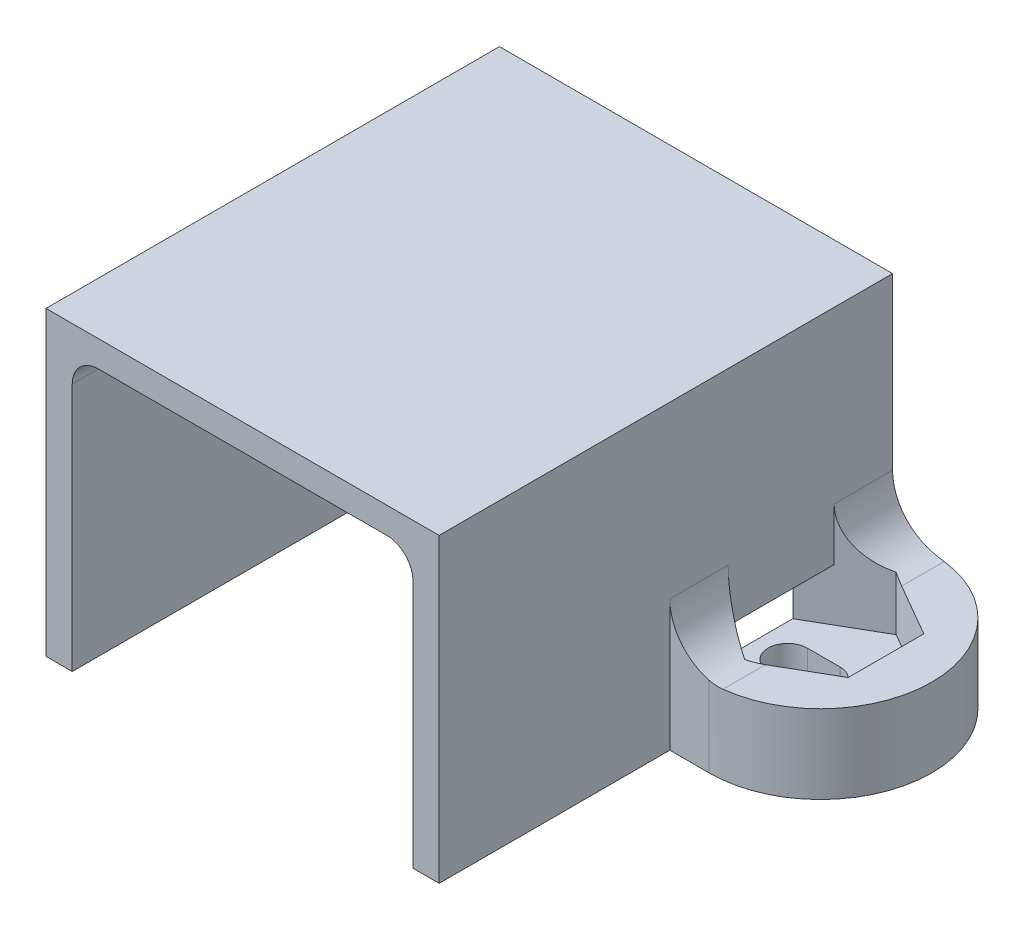
SolidWorks part; units mm, degrees
material "ABS"
ref_plane "Front" through (0, 0, 0) normal (0, 0, 1) x (1, 0, 0)
ref_plane "Top" through (0, 0, 0) normal (0, 1, 0) x (1, 0, 0)
ref_plane "Right" through (0, 0, 0) normal (1, 0, 0) x (0, 0, -1)
sketch "Sketch1" plane through (0, 0, 0) normal (0, 0, 1) x (1, 0, 0)
  line L1 (0, 0) -> (15, 0)
  line L2 (0, 0) -> (0, 11.5)
  line L3 (0, 11.5) -> (15, 11.5)
  line L4 (15, 0) -> (15, 11.5)
  dimension "D1" = 11.5
  dimension "D2" = 15
extrude "Boss-Extrude1" add sketch "Sketch1" against normal blind 17.3
sketch "Sketch2" plane through (0, 0, 0) normal (0, 0, 1) x (1, 0, 0)
  line L0 (0, 0) -> (15, 0) construction
  line L1 (1, 0) -> (14, 0)
  line L2 (1, 0) -> (1, 10.5)
  line L3 (1, 10.5) -> (14, 10.5)
  line L4 (14, 0) -> (14, 10.5)
  line L5 (0, 11.5) -> (0, 0) construction
  dimension "D1" = 10.5
  dimension "D2" = 13
  dimension "D3" = 1
extrude "Cut-Extrude1" cut sketch "Sketch2" against normal through all
fillet "Fillet1" radius 1 2 edges at (14, 10.5, -8.65) (1, 10.5, -8.65)
sketch "Sketch7" plane through (0, 0, 0) normal (0, -1, 0) x (1, 0, 0)
  line L1 (0, -17.3) -> (-1.5, -17.3)
  line L2 (0, -17.3) -> (0, -8.8)
  line L3 (0, -8.8) -> (-1.5, -8.8)
  line L4 (-1.5, -17.3) -> (-1.5, -8.8)
  line L5 (15, -17.3) -> (16.5, -17.3)
  line L6 (15, -17.3) -> (15, -8.8)
  line L7 (15, -8.8) -> (16.5, -8.8)
  line L8 (16.5, -17.3) -> (16.5, -8.8)
  dimension "D1" = 8.5
  dimension "D2" = 8.5
  dimension "D3" = 1.5
  dimension "D4" = 1.5
extrude "Boss-Extrude4" add sketch "Sketch7" against normal blind 3
sketch "Sketch11" plane through (0, 0, 0) normal (0, -1, 0) x (1, 0, 0)
  line L6 (1, -17.3) -> (1, 0)
  line L7 (1, 0) -> (0, 0)
  line L8 (0, 0) -> (0, -8.8)
  line L9 (0, -8.8) -> (-1.5, -8.8)
  line L10 (-1.5, -8.8) -> (-1.5, -17.3)
  line L11 (-1.5, -17.3) -> (1, -17.3)
  line L16 (-1.5, -8.8) -> (-1.5, -17.3)
  arc A0 (-1.5, -8.8) -> (-1.5, -17.3) centre (-1.5, -13.05) ccw
  dimension "D1" = 0
extrude "Boss-Extrude5" add sketch "Sketch11" against normal blind 3
sketch "Sketch12" plane through (0, 0, 0) normal (0, -1, 0) x (1, 0, 0)
  line L6 (14, 0) -> (14, -17.3)
  line L7 (14, -17.3) -> (16.5, -17.3)
  line L8 (16.5, -17.3) -> (16.5, -8.8)
  line L9 (16.5, -8.8) -> (15, -8.8)
  line L10 (15, -8.8) -> (15, 0)
  line L11 (15, 0) -> (14, 0)
  line L12 (14, 0) -> (14, -17.3)
  line L13 (14, -17.3) -> (16.5, -17.3)
  line L15 (16.5, -8.8) -> (15, -8.8)
  line L16 (15, -8.8) -> (15, 0)
  line L17 (15, 0) -> (14, 0)
  arc A0 (16.5, -8.8) -> (16.5, -17.3) centre (16.5, -13.05) cw
  dimension "D1" = 0
extrude "Boss-Extrude6" add sketch "Sketch12" against normal blind 3
sketch "Sketch13" plane through (0, 3, 0) normal (0, 1, 0) x (1, 0, 0)
  line L0 (0, 13.05) -> (-0.25, 13.05) construction
  line L1 (0, 17.3) -> (0, 8.8) construction
  line L2 (-0.25, 13.05) -> (-1.5, 13.05) construction
  line L3 (-0.25, 12.3) -> (-1.5, 12.3)
  line L4 (-0.25, 13.8) -> (-1.5, 13.8)
  line L5 (15, 13.05) -> (15.25, 13.05) construction
  line L6 (15, 8.8) -> (15, 17.3) construction
  line L7 (15.25, 13.05) -> (16.5, 13.05) construction
  line L8 (15.25, 13.8) -> (16.5, 13.8)
  line L9 (15.25, 12.3) -> (16.5, 12.3)
  arc A0 (-0.25, 12.3) -> (-0.25, 13.8) centre (-0.25, 13.05) ccw
  arc A1 (-1.5, 13.8) -> (-1.5, 12.3) centre (-1.5, 13.05) ccw
  arc A2 (15.25, 13.8) -> (15.25, 12.3) centre (15.25, 13.05) ccw
  arc A3 (16.5, 12.3) -> (16.5, 13.8) centre (16.5, 13.05) ccw
  point P4 (-0.875, 13.05)
  point P14 (15.875, 13.05)
  dimension "D1" = 0.25
  dimension "D2" = 1.5
  dimension "D3" = 0.25
  dimension "D4" = 1.5
  dimension "D5" = 1.5
  dimension "D6" = 1.5
extrude "Cut-Extrude4" cut sketch "Sketch13" against normal through all
sketch "Sketch14" plane through (0, 3, 0) normal (0, 1, 0) x (1, 0, 0)
  line L1 (-1.5, 15.9368) -> (-4, 14.4934)
  line L2 (-4, 14.4934) -> (-4, 11.6066)
  line L3 (-4, 11.6066) -> (-1.5, 10.1632)
  line L4 (-1.5, 10.1632) -> (1, 11.6066)
  line L5 (1, 11.6066) -> (1, 14.4934)
  line L6 (1, 14.4934) -> (-1.5, 15.9368)
  line L7 (16.5, 15.9368) -> (14, 14.4934)
  line L8 (14, 14.4934) -> (14, 11.6066)
  line L9 (14, 11.6066) -> (16.5, 10.1632)
  line L10 (16.5, 10.1632) -> (19, 11.6066)
  line L11 (19, 11.6066) -> (19, 14.4934)
  line L12 (19, 14.4934) -> (16.5, 15.9368)
  circle A0 centre (-1.5, 13.05) radius 2.5 construction
  arc A1 (-1.5, 17.3) -> (-1.5, 8.8) centre (-1.5, 13.05) ccw construction
  circle A3 centre (16.5, 13.05) radius 2.5 construction
  arc A4 (16.5, 8.8) -> (16.5, 17.3) centre (16.5, 13.05) ccw construction
  point P9 (-5.75, 13.05)
  point P13 (20.75, 13.05)
  dimension "D1" = 5
  dimension "D2" = 4.25
  dimension "D3" = 5
  dimension "D4" = 4.25
extrude "Cut-Extrude5" cut sketch "Sketch14" against normal blind 2
fillet "Fillet6" radius 2 4 edges
